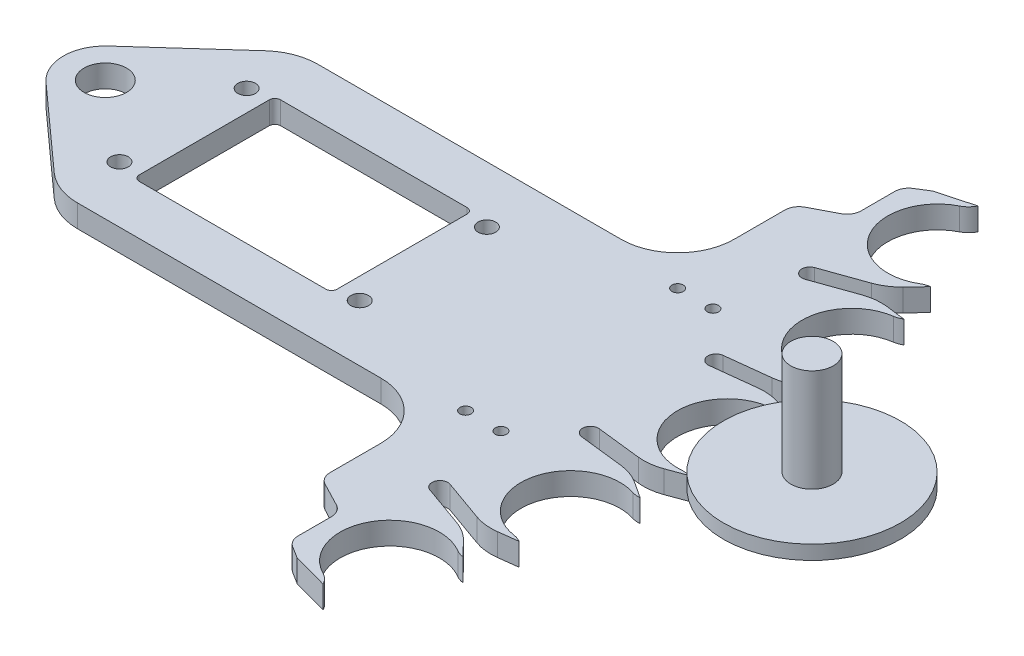
SolidWorks part; units mm, degrees
material "6061 Alloy"
ref_plane "Front Plane" through (0, 0, 0) normal (0, 0, 1) x (1, 0, 0)
ref_plane "Top Plane" through (0, 0, 0) normal (0, 1, 0) x (1, 0, 0)
ref_plane "Right Plane" through (0, 0, 0) normal (1, 0, 0) x (0, 0, -1)
sketch "Sketch1" plane through (0, 0, 0) normal (0, 1, 0) x (1, 0, 0)
  line L0 (79.0087, -38.7509) -> (82.9038, -29.5121) construction
  line L2 (0, 0) -> (79.0087, -38.7509) construction
  line L3 (82.9038, -29.5121) -> (0, 0) construction
  line L61 (92.2842, -32.8513) -> (73.5234, -26.1728) construction
  line L64 (163.1245, 0) -> (-55.0575, 0) construction
  line L65 (91.9069, -33.9111) -> (73.1461, -27.2327) construction
  line L66 (92.6614, -31.7914) -> (73.9007, -25.113) construction
  line L67 (84.4041, -31.2403) -> (73.1461, -27.2327)
  line L70 (85.1586, -29.1206) -> (73.9007, -25.113)
  line L72 (89.2809, -11.3545) -> (77.4085, -9.9951)
  line L73 (89.5368, -9.1191) -> (77.6644, -7.7597)
  line L74 (89.5368, 9.1191) -> (77.6644, 7.7597)
  line L75 (89.2809, 11.3545) -> (77.4085, 9.9951)
  line L76 (85.1586, 29.1206) -> (73.9007, 25.113)
  line L77 (84.4041, 31.2403) -> (73.1461, 27.2327)
  line L79 (76.3729, 47.6149) -> (63.9823, 39.89) construction
  line L80 (76.3729, 47.6149) -> (66.3121, 41.1665) [skipped]
  line L81 (75.1587, 49.5092) -> (65.098, 43.0608) [skipped]
  line L82 (63.9823, 39.89) -> (63.9823, 17) construction
  line L83 (63.9823, 17) -> (10, 17)
  line L86 (63.9823, -17) -> (10, -17)
  line L87 (63.9823, -39.89) -> (63.9823, -17) construction
  line L88 (76.3729, -47.6149) -> (63.9823, -39.89) construction
  line L90 (76.3729, 47.6149) -> (69.4823, 43.319)
  line L91 (69.4823, 43.319) -> (69.4823, 36.2602)
  line L92 (69.4823, 36.2602) -> (63.9823, 33.39)
  line L93 (63.9823, 33.39) -> (63.9823, 17)
  line L94 (63.9823, -33.39) -> (63.9823, -17)
  line L95 (69.4823, -36.2602) -> (63.9823, -33.39)
  line L96 (69.4823, -43.319) -> (69.4823, -36.2602)
  line L97 (76.3729, -47.6149) -> (69.4823, -43.319)
  line L98 (10, 17) -> (-3.9761, 4.4159)
  line L99 (-3.9761, -4.4159) -> (10, -17)
  circle A1 centre (79.0087, -38.7509) radius 10.0263 construction
  circle A2 centre (0, 0) radius 88 construction
  arc A89 (91.9069, -33.9111) -> (92.6614, -31.7914) centre (92.2842, -32.8513) ccw construction
  arc A90 (73.9007, -25.113) -> (73.1461, -27.2327) centre (73.5234, -26.1728) ccw construction
  circle A91 centre (79.0087, -38.7509) radius 7.0263 construction
  arc A92 (73.9007, -25.113) -> (73.1461, -27.2327) centre (73.5234, -26.1728) ccw
  circle A93 centre (0, 0) radius 90 construction
  arc A94 (84.4041, -31.2403) -> (83.5703, -33.4066) centre (0, 0) cw
  arc A95 (83.5703, -33.4066) -> (77.5755, -45.6295) centre (79.0087, -38.7509) ccw
  arc A96 (77.5755, -45.6295) -> (76.3729, -47.6149) centre (0, 0) cw
  arc A97 (85.8813, -26.9147) -> (85.1586, -29.1206) centre (0, 0) cw
  arc A98 (88.9584, -13.6532) -> (85.8813, -26.9147) centre (85.7227, -19.8902) ccw
  arc A99 (89.2809, -11.3545) -> (88.9584, -13.6532) centre (0, 0) cw
  arc A100 (77.6644, -7.7597) -> (77.4085, -9.9951) centre (77.5365, -8.8774) ccw
  arc A101 (89.7422, -6.8069) -> (89.5368, -9.1191) centre (0, 0) cw
  arc A102 (89.7422, 6.8069) -> (89.7422, -6.8069) centre (88, 0) ccw
  arc A103 (89.5368, 9.1191) -> (89.7422, 6.8069) centre (0, 0) cw
  arc A104 (77.4085, 9.9951) -> (77.6644, 7.7597) centre (77.5365, 8.8774) ccw
  arc A105 (88.9584, 13.6532) -> (89.2809, 11.3545) centre (0, 0) cw
  arc A106 (85.8813, 26.9147) -> (88.9584, 13.6532) centre (85.7227, 19.8902) ccw
  arc A107 (85.1586, 29.1206) -> (85.8813, 26.9147) centre (0, 0) cw
  arc A108 (73.1461, 27.2327) -> (73.9007, 25.113) centre (73.5234, 26.1728) ccw
  arc A109 (83.5703, 33.4066) -> (84.4041, 31.2403) centre (0, 0) cw
  arc A110 (77.5755, 45.6295) -> (83.5703, 33.4066) centre (79.0087, 38.7509) ccw
  arc A111 (76.3729, 47.6149) -> (77.5755, 45.6295) centre (0, 0) cw
  arc A112 (-3.9761, 4.4159) -> (-3.9761, -4.4159) centre (0, 0) ccw
  circle A177 centre (0, 0) radius 2
  arc A178 (65.098, 43.0608) -> (66.3121, 41.1665) centre (65.705, 42.1136) ccw [skipped]
  point P2 (82.9038, -29.5121)
  point P27 (80.9737, 0)
  point P36 (71.9823, 38.7509)
  point P65 (0, 0)
  dimension "D9" = 4
  dimension "D1" = 176
  dimension "D6" = 14.0527
  dimension "D8" = 180
  dimension "D2" = 10.0263
  dimension "D4" = 2.25
  dimension "D5" = 9.957
  dimension "D11" = 34
  dimension "D12" = 8
  dimension "D13" = 2.5
  dimension "D14" = 6.5
  dimension "D3" = 10
  dimension "D10" = 138
  dimension "D7" = 5
extrude "Base Boss-Extrude1" add sketch "Sketch1" along normal blind 3.175
sketch "Sketch4" plane through (0, 3.175, 0) normal (0, 1, 0) x (1, 0, 0)
  line L0 (100, 0) -> (100.5703, 10.0101) construction
  line L1 (0, 0) -> (100, 0) construction
  line L2 (100.5703, 10.0101) -> (106.9013, 121.1445) construction
  line L3 (100, 0) -> (106.9013, 0) construction
  line L4 (106.9013, 0) -> (106.9013, 121.1445) construction
  circle A0 centre (100, 0) radius 12.5263
  circle A1 centre (100, 0) radius 6.9013
  circle A2 centre (106.9013, 121.1445) radius 121.1445
  circle A3 centre (100.5703, 10.0101) radius 1
  point P7 (101.5703, 10.0101)
  point P8 (112.5263, 0)
  point P9 (100.7124, 12.5061)
  point P13 (100.6271, 11.0085)
  dimension "D2" = 2
  dimension "D4" = 13.8027
  dimension "D1" = 10.0263
  dimension "D5" = 100
  dimension "D3" = 121.1445
  dimension "D6" = 1.5
extrude "Boss-Extrude2" add sketch "Sketch4" along normal blind 2 separate body contours A0
extrude "Boss-Extrude3" add sketch "Sketch4<3>" against normal blind 3.175 contours A2 A1 | A3 region at (99.8414, 3.175, 2.7832) region at (100.5703, 3.175, -10.0101)
sketch "Sketch4<3>" plane through (0, 3.175, 0) normal (0, 1, 0) x (1, 0, 0) same geometry as "Sketch4"
sketch "Sketch6" plane through (0, 5.175, 0) normal (0, 1, 0) x (1, 0, 0)
  circle A0 centre (100, 0) radius 3
  circle A1 centre (100, 0) radius 2
  dimension "D1" = 6
  dimension "D2" = 4
extrude "Boss-Extrude4" add sketch "Sketch6" along normal blind 16.5 from surface contours A0 starting at face at (100.5703, 3.175, -9.0101)
sketch "Sketch7" plane through (0, 3.175, 0) normal (0, 1, 0) x (1, 0, 0)
  line L0 (0, 0) -> (83.9584, 0) construction
  line L1 (14, 10) -> (42, 10)
  line L2 (14, 10) -> (14, -10)
  line L3 (14, -10) -> (42, -10)
  line L4 (42, 10) -> (42, -10)
  line L5 (43, 9) -> (43, -9.1197) construction
  dimension "D1" = 28
  dimension "D2" = 20
  dimension "D3" = 1
extrude "Rectangle Cut-Extrude1" cut sketch "Sketch7" against normal blind 10
hole_wizard "M3x0.5 Tapped Hole1" positions "Sketch2" profile "Sketch3" tap size "M3x0.5" standard "ANSI Metric" end condition through all
sketch "Sketch2" plane through (0, 3.175, 0) normal (0, 1, 0) x (1, 0, 0)
  line L0 (0, 0) -> (80.9737, 0) construction
  line L1 (14, 10) -> (14, -10) construction
  line L2 (42, -10) -> (42, 10) construction
  arc A0 (89.7422, 6.8069) -> (89.7422, -6.8069) centre (88, 0) ccw construction
  point P11 (45, 9)
  point P20 (11, 9)
  point P42 (45, -9)
  point P43 (11, -9)
  dimension "D1" = 3
  dimension "D2" = 3
  dimension "D3" = 9
  dimension "D4" = 9
sketch "Sketch3" plane through (45, 3.175, -9) normal (1, 0, 0) x (0, 0, 1)
  line L0 (0, 0) -> (0, 3.175)
  line L1 (0, 3.175) -> (1.25, 3.175)
  line L2 (1.25, 3.175) -> (1.25, 0)
  line L5 (1.25, 0) -> (0, 0)
  line L11 (0, -6.35) -> (0, 107.95) construction
  dimension "Thru Tap Drill Dia." = 2.5
  dimension "Thru Tap Drill Depth" = 3.175
cosmetic thread "Hole Thread11" parameters "D2"=3
cosmetic thread "Hole Thread12" parameters "D2"=3
cosmetic thread "Hole Thread13" parameters "D2"=3
cosmetic thread "Hole Thread15" parameters "D2"=3
ref_axis "Axis1" through (0, 3.175, 0) along (0, -1, 0)
chamfer "Chamfer1" distance 4 distance2 2 4 edges at (84.4041, 1.5875, -31.2403) (89.2809, 1.5875, -11.3545) (85.1586, 1.5875, 29.1206) (89.5368, 1.5875, 9.1191) first distance on face at (78.7751, 1.5875, -29.2365) first distance on face at (83.3447, 1.5875, -10.6748) first distance on face at (79.5297, 1.5875, 27.1168) first distance on face at (83.6006, 1.5875, 8.4394)
chamfer "Chamfer2" distance 2 distance2 4 4 edges at (85.1586, 1.5875, -29.1206) (84.4041, 1.5875, 31.2403) (89.2809, 1.5875, 11.3545) (89.5368, 1.5875, -9.1191) first distance on face at (85.5235, 1.5875, -28.0188) first distance on face at (83.9907, 1.5875, 32.3248) first distance on face at (89.1233, 1.5875, 12.5043) first distance on face at (89.6432, 1.5875, -7.9633)
chamfer "Chamfer3" distance 5 distance2 1.5 1 edges at (76.3729, 1.5875, 47.6149) first distance on face at (72.9276, 1.5875, 45.467)
chamfer "Chamfer4" distance 1.5 distance2 5 1 edges at (76.3729, 1.5875, -47.6149) first distance on face at (76.9774, 1.5875, -46.6241)
fillet "Fillet9" radius 3 10 edges at (77.5755, 1.5875, 45.6295) (83.5703, 1.5875, 33.4066) (85.8813, 1.5875, 26.9147) (88.9584, 1.5875, 13.6532) (89.7422, 1.5875, 6.8069) (89.7422, 1.5875, -6.8069) (88.9584, 1.5875, -13.6532) (85.8813, 1.5875, -26.9147) (83.5703, 1.5875, -33.4066) (77.5755, 1.5875, -45.6295)
fillet "Fillet10" radius 7 8 edges at (81.3903, 1.5875, -27.7791) (80.6357, 1.5875, -29.8988) (81.3903, 1.5875, 27.7791) (80.6357, 1.5875, 29.8988) (85.3068, 1.5875, 10.8994) (85.5628, 1.5875, 8.6641) (85.5628, 1.5875, -8.6641) (85.3068, 1.5875, -10.8994)
fillet "Fillet6" radius 2 6 edges at (69.4823, 1.5875, 43.319) (69.4823, 1.5875, 36.2602) (63.9823, 1.5875, 33.39) (63.9823, 1.5875, -33.39) (69.4823, 1.5875, -36.2602) (69.4823, 1.5875, -43.319)
fillet "Fillet7" radius 0.8 4 edges at (14, 1.5875, 10) (42, 1.5875, 10) (42, 1.5875, -10) (14, 1.5875, -10)
sketch "Sketch8" plane through (0, 3.175, 0) normal (0, 1, 0) x (1, 0, 0)
  circle A0 centre (0, 0) radius 3
  dimension "D1" = 6
extrude "Cut-Extrude1" cut sketch "Sketch8" against normal through all
fillet "Fillet1" radius 8 4 edges at (63.9823, 1.5875, 17) (63.9823, 1.5875, -17) (10, 1.5875, -17) (10, 1.5875, 17)
sketch "Sketch15" plane through (0, 3.175, 0) normal (0, 1, 0) x (1, 0, 0)
  line L0 (0, 0) -> (97.4982, 0) construction
  line L1 (63.9823, 32.1778) -> (63.9823, 25) construction
  circle A0 centre (70.9823, -15) radius 1
  circle A1 centre (70.9823, 15) radius 1
  circle A2 centre (65.9823, -15) radius 1
  circle A3 centre (65.9823, 15) radius 1
  dimension "D1" = 2
  dimension "D4" = 5
  dimension "D2" = 15
  dimension "D3" = 7
hole_wizard "M2 Tapped Hole1" positions "Sketch16" profile "Sketch17" tap size "M2" standard "ISO"
sketch "Sketch16" plane through (0, 3.175, 0) normal (0, 1, 0) x (1, 0, 0)
  point P0 (70.9823, -15)
  point P3 (70.9823, 15)
  point P6 (65.9823, 15)
  point P9 (65.9823, -15)
sketch "Sketch17" plane through (70.9823, 3.175, 15) normal (1, 0, 0) x (0, 0, 1)
  line L0 (0, 0) -> (0, 6.4807)
  line L1 (0, 6.4807) -> (0.8, 6)
  line L2 (0.8, 6) -> (0.8, 0)
  line L5 (0.8, 0) -> (0, 0)
  line L10 (0, 6.4807) -> (-0.8, 6) construction
  line L11 (0, -6.35) -> (0, 107.95) construction
  dimension "Tap Drill Dia." = 1.6
  dimension "Tap Drill Depth" = 6
  dimension "Drill Angle" = 118
cosmetic thread "Hole Thread18" parameters "D1"=4, "D2"=2
cosmetic thread "Hole Thread19" parameters "D1"=4, "D2"=2
cosmetic thread "Hole Thread20" parameters "D1"=4, "D2"=2
cosmetic thread "Hole Thread21" parameters "D1"=4, "D2"=2
equation "\"GenevaWheelRadius\"= 88"
equation "\"D1@Sketch1\"=\"GenevaWheelRadius\" * 2 "
equation "\"GenevaPinionRadius\"= sqr ( \"CenterDistance\" ^ 2 - \"GenevaWheelRadius\" ^ 2 )"
equation "\"D2@Sketch1\"=\"GenevaPinionRadius\""
equation "\"StepAngle\"= 13"
equation "\"Steps\"= 360 / \"StepAngle\""
equation "\"PinionPinDia\"=2"
equation "\"Clearance\"= 0.25"
equation "\"CenterDistance\"= \"GenevaWheelRadius\" / cos ( 180 / \"Steps\" )"
equation "\"D4@Sketch1\"=\"PinionPinDia\" +\"Clearance\""
equation "\"D5@Sketch1\"=\"GenevaWheelRadius\" + \"GenevaPinionRadius\" - \"CenterDistance\"+0.5"
equation "\"D6@Sketch1\"=(\"GenevaPinionRadius\"-\"PinionPinDia\"*1.5)*2"
equation "\"D8@Sketch1\"=2*\"GenevaWheelRadius\" - 1 + 2*\"Extension Constant\""
equation "\"D1@Sketch4\"=\"GenevaPinionRadius\""
equation "\"D2@Sketch4\"=\"PinionPinDia\""
equation "\"D4@Sketch4\"=2*(\"GenevaPinionRadius\"-\"PinionPinDia\"*1.5 )-\"Clearance\""
equation "\"D3@Sketch4\"=\"GenevaWheelRadius\" * (2*(\"GenevaPinionRadius\"-(\"PinionPinDia\"*1.5)) - \"Clearance\")/\"GenevaPinionRadius\""
equation "\"D4@Sketch2\"=\"D3@Sketch2\""
equation "\"Extension Constant\"= 2.5mm"
